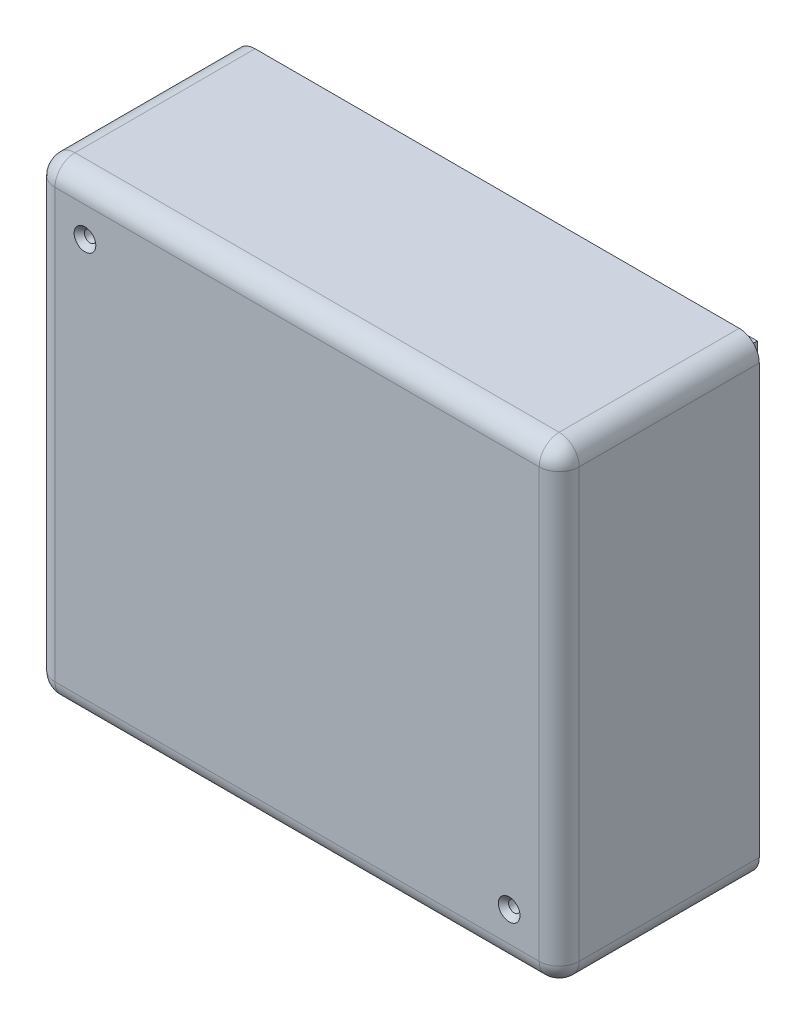
SolidWorks part; units mm, degrees
note: The reader was unsure of these and kept them because the rebuilt part matched: shared geometry of "Sketch3<5>".
ref_plane "Front Plane" through (0, 0, 0) normal (0, 0, 1) x (1, 0, 0)
ref_plane "Top Plane" through (0, 0, 0) normal (0, 1, 0) x (1, 0, 0)
ref_plane "Right Plane" through (0, 0, 0) normal (1, 0, 0) x (0, 0, -1)
sketch "Sketch1" plane through (0, 0, 0) normal (1, 0, 0) x (0, 0, -1)
  line L0 (20.0215, 118.8858) -> (20.0215, 0.0138) construction
  dimension "D1" = 118.872
sketch "Sketch2" plane through (0, 0, 0) normal (0, 0, 1) x (1, 0, 0)
  line L0 (-0.0254, 118.7551) -> (133.0706, 118.7551) construction
  dimension "D1" = 133.096
sketch "Sketch3" plane through (0, 0, 0) normal (0, 0, 1) x (1, 0, 0)
  line L1 (0, 118.872) -> (133.096, 118.872)
  line L2 (0, 118.872) -> (0, 0)
  line L3 (0, 0) -> (133.096, 0)
  line L4 (133.096, 118.872) -> (133.096, 0)
  line L5 (3.048, 115.824) -> (130.048, 115.824)
  line L6 (3.048, 115.824) -> (3.048, 74.168)
  line L7 (3.048, 3.048) -> (130.048, 3.048)
  line L8 (130.048, 115.824) -> (130.048, 3.048)
  line L9 (5.588, 113.284) -> (127.508, 113.284)
  line L10 (5.588, 113.284) -> (5.588, 74.168)
  line L11 (5.588, 5.588) -> (127.508, 5.588)
  line L12 (127.508, 113.284) -> (127.508, 5.588)
  line L14 (3.048, 11.684) -> (3.048, 3.048)
  line L15 (5.588, 11.684) -> (5.588, 5.588)
  line L16 (3.048, 11.684) -> (3.048, 74.168)
  line L17 (5.588, 74.168) -> (5.588, 11.684)
  dimension "D1" = 133.096
  dimension "D2" = 118.872
  dimension "D3" = 3.048
  dimension "D4" = 3.048
  dimension "D5" = 3.048
  dimension "D6" = 3.048
  dimension "D7" = 2.54
  dimension "D8" = 2.54
  dimension "D9" = 2.54
  dimension "D10" = 2.54
extrude "Boss-Extrude1" add sketch "Sketch3" along normal blind 50.8 contours L3 L4 L1 L2
extrude "Boss-Extrude2" add sketch "Sketch3<5>" against normal blind 2.54 contours L10 L17 L15 L11 L12 L9 | L4 L1 L2 L3 L14 L16 L6 L5 L8 L7
sketch "Sketch3<5>" plane through (0, 0, 0) normal (0, 0, 1) x (1, 0, 0) same geometry as "Sketch3"
sketch "Sketch11" plane through (0, 0, 0) normal (0, 0, -1) x (-1, 0, 0)
  line L1 (-127.508, 113.284) -> (-5.588, 113.284)
  line L2 (-127.508, 113.284) -> (-127.508, 5.588)
  line L3 (-127.508, 5.588) -> (-5.588, 5.588)
  line L4 (-5.588, 113.284) -> (-5.588, 5.588)
extrude "Cut-Extrude1" cut sketch "Sketch11" against normal blind 46.99
sketch "Sketch12" plane through (0, 0, 0) normal (-1, 0, 0) x (0, 0, 1)
  line L0 (-2.54, 74.168) -> (13.916, 74.168)
  line L1 (-2.54, 115.824) -> (-2.54, 3.048) construction
  line L2 (13.916, 74.168) -> (13.916, 11.684)
  line L3 (13.916, 11.684) -> (-2.54, 11.684)
  line L5 (-2.54, 11.684) -> (-2.54, 74.168)
  line L6 (50.8, 118.872) -> (0, 118.872) construction
  line L7 (50.8, 0) -> (0, 0) construction
  dimension "D1" = 44.704
  dimension "D2" = 11.684
extrude "Cut-Extrude2" cut sketch "Sketch12" along direction (-1, 0, 0) on the side against the normal blind 12.7
fillet "Fillet1" radius 5.08 8 edges at (66.548, 118.872, 50.8) (0, 59.436, 50.8) (66.548, 0, 50.8) (133.096, 59.436, 50.8) (133.096, 0, 25.4) (133.096, 118.872, 25.4) (0, 118.872, 25.4) (0, 0, 25.4)
sketch "Sketch13" plane through (0, 0, 50.8) normal (0, 0, 1) x (1, 0, 0)
  line L0 (0, 5.08) -> (0, 113.792) construction
  line L1 (5.08, 118.872) -> (128.016, 118.872) construction
  line L2 (133.096, 113.792) -> (133.096, 5.08) construction
  line L3 (128.016, 0) -> (5.08, 0) construction
  circle A0 centre (12.7, 106.172) radius 4.064
  circle A1 centre (120.396, 12.7) radius 4.064
  dimension "D1" = 8.128
  dimension "D2" = 8.128
  dimension "D3" = 12.7
  dimension "D4" = 12.7
  dimension "D5" = 12.7
  dimension "D6" = 12.7
hole_wizard "CSK for M2.5 Flat Head Machine Screw1" positions "Sketch14" profile "Sketch15" countersink size "M2.5" standard "ANSI Metric"
sketch "Sketch14" plane through (0, 0, 50.8) normal (0, 0, 1) x (1, 0, 0)
  point P0 (12.7, 106.172)
  point P3 (120.396, 12.7)
sketch "Sketch15" plane through (12.7, 106.172, 50.8) normal (1, 0, 0) x (0, -1, 0)
  line L0 (0, 0) -> (0, 5.9512)
  line L1 (0, 5.9512) -> (1.45, 5.08)
  line L2 (1.45, 5.08) -> (1.45, 1.3)
  line L3 (1.45, 1.3) -> (2.75, 0)
  line L5 (2.75, 0) -> (0, 0)
  line L6 (-1.45, 1.3) -> (-2.75, 0) construction
  line L10 (0, 5.9512) -> (-1.45, 5.08) construction
  line L11 (0, -6.35) -> (0, 107.95) construction
  dimension "Hole Dia." = 2.9
  dimension "Hole Depth" = 5.08
  dimension "Near C'Sink Dia." = 5.5
  dimension "Near C'Sink Angle" = 90
  dimension "Drill Angle" = 118
